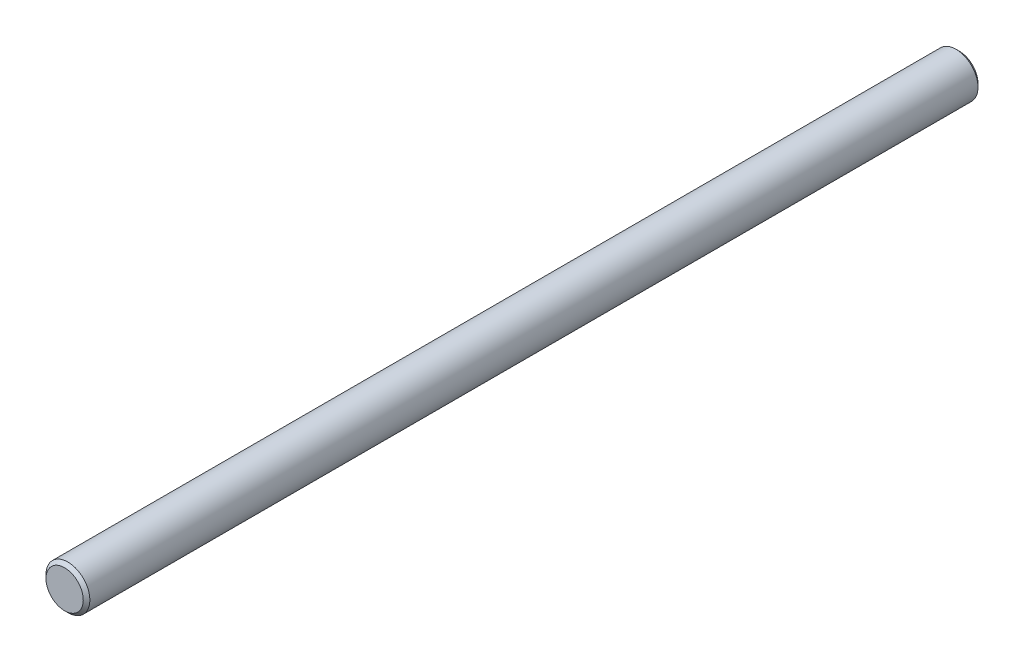
SolidWorks part; units mm, degrees
ref_plane "Front Plane" through (0, 0, 0) normal (0, 0, 1) x (1, 0, 0)
ref_plane "Top Plane" through (0, 0, 0) normal (0, 1, 0) x (1, 0, 0)
ref_plane "Right Plane" through (0, 0, 0) normal (1, 0, 0) x (0, 0, -1)
sketch "Sketch1" plane through (0, 0, 0) normal (1, 0, 0) x (0, 0, -1)
  line L0 (80.9244, 0) -> (-80.9244, 0) construction
  line L1 (-80.9244, -3.9688) -> (-80.9244, 3.9687) construction
  line L2 (-80.9244, 3.9687) -> (-82.3355, 3.9687) construction
  line L3 (80.9244, 3.9687) -> (80.9244, -3.9687) construction
  point P3 (80.9244, 3.9687)
  point P4 (0, 0)
  point P7 (-80.9244, 0)
  point P8 (-77.3966, -3.9688)
  point P12 (-69.0182, 3.9687)
  point P13 (80.9244, 0)
  point P15 (69.0182, 3.9688)
  point P19 (19.2645, -3.9688)
  dimension "OD" = 7.9375
  dimension "Pitch" = 1.4111
  dimension "Length" = 161.8488
  dimension "D1" = 3.5278
  dimension "D4" = 11.9062
  dimension "D5" = 11.9062
  dimension "SL" = 100.1889
sketch "Sketch2" plane through (0, 0, 0) normal (0, 0, 1) x (1, 0, 0)
  line L0 (0, -3.9688) -> (0, 3.9687) construction
  line L1 (-3.9687, 0) -> (3.9687, 0) construction
  circle A0 centre (0, 0) radius 3.9687
extrude "Boss-Extrude1" add sketch "Sketch2" along normal up to vertex (80.9244 mm away) and the other way up to vertex (80.9244 mm away) up to point (0, 0, 80.9244) other way up to point (0, 0, -80.9244)
chamfer "Chamfer1" distance 0.5953 angle 45 2 edges at (3.9687, 0, -80.9244) (3.9687, 0, 80.9244)
ref_axis "Center Axis 1" through (0, 0, -80.9244) along (0, 0, 1)
sketch "Sketch13" [suppressed] plane through (0, 0, 457.2) normal (0, 0, 1) x (1, 0, 0)
  circle A0 centre (0, 0) radius 3.9687
curve "Helix/Spiral1" [suppressed] pitch 1.4111 height 101.6 turns 72
sketch "Sketch14" [suppressed] plane through (0, 0, 0) normal (1, 0, 0) x (0, 0, -1)
  line L0 (-458.5229, 4.1215) -> (-457.8174, 2.8994) construction
  line L1 (-457.8174, 2.8994) -> (-457.1118, 4.1215) construction
  line L2 (-457.1118, 4.1215) -> (-458.5229, 4.1215) construction
  line L3 (-457.8174, 4.1215) -> (-457.8174, 3.9687) construction
  line L4 (-457.8174, 3.9687) -> (-457.8174, 3.0522) construction
  line L5 (-457.8174, 3.0522) -> (-457.8174, 2.8994) construction
  line L6 (-458.4347, 3.9687) -> (-457.2, 3.9687) construction
  line L8 (-457.1559, 4.0451) -> (-458.4788, 4.0451) construction
  line L9 (-457.9056, 3.0522) -> (-457.7292, 3.0522)
  line L10 (-457.9056, 3.0522) -> (-457.7292, 3.0522) construction
  line L11 (-457.7292, 3.0522) -> (-457.1559, 4.0451)
  line L12 (-457.1559, 4.0451) -> (-458.4788, 4.0451)
  line L13 (-458.4788, 4.0451) -> (-457.9056, 3.0522)
  point P9 (-457.8174, 3.0522)
  point P14 (-457.8174, 3.9687)
  point P16 (-457.8174, 4.0451)
  point P17 (-457.8174, 4.0451)
  dimension "D1" = 1.4111
  dimension "D2" = 0.1764
sweep "Cut-Sweep1" [suppressed] cut profiles "Sketch14" path "Helix/Spiral1"
pattern_linear "LPattern1" [suppressed] count 10 spacing 100.1889 along (0, 0, -1) of bodies 503
ref_axis "Axis1" through (0, 0, 55.88) along (0, 0, -1)
equation "\"D1@Chamfer1\"=\"OD@Sketch1\"*.075"
equation "\"D4@Sketch1\"=\"OD@Sketch1\"*1.5"
equation "\"D5@Sketch1\"=\"OD@Sketch1\"*1.5"
equation "\"SL@Sketch1\"=\"Pitch@Sketch1\"*71"
equation "\"D4@Helix/Spiral1\"=\"Pitch@Sketch1\""
equation "\"D5@Helix/Spiral1\"= ( \"SL@Sketch1\" / \"Pitch@Sketch1\" ) + 1"
equation "\"D1@Sketch14\"=\"Pitch@Sketch1\""
equation "\"D2@Sketch14\"=\"D1@Sketch14\"/8"
equation "\"D3@LPattern1\"=\"SL@Sketch1\""
equation "\"D1@Sketch1\"=\"Pitch@Sketch1\"*2.5"
